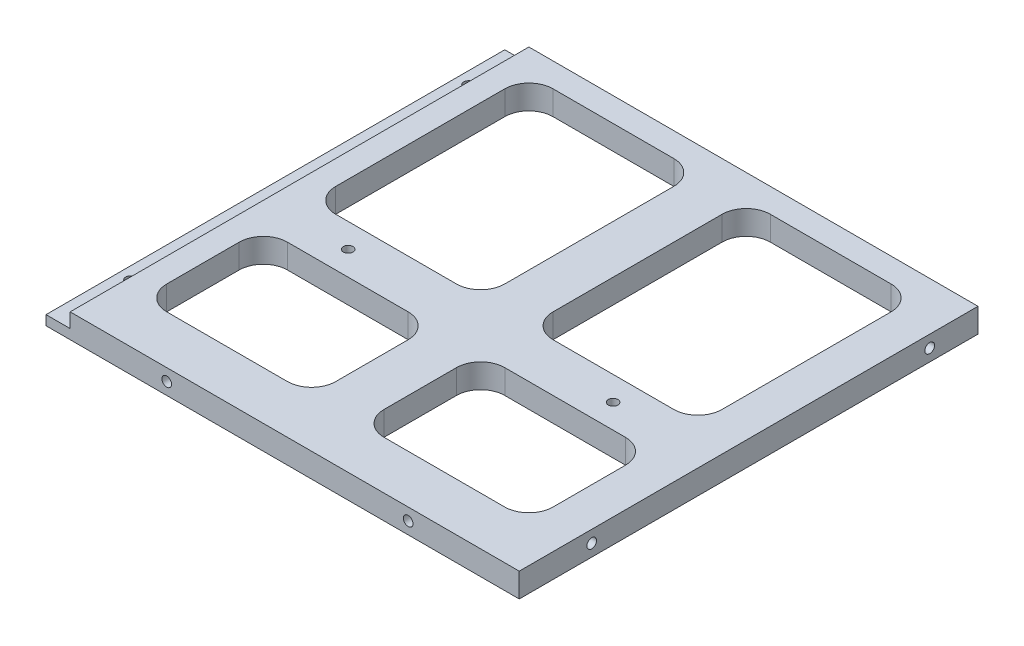
SolidWorks part; units mm, degrees
ref_plane "Front Plane" through (0, 0, 0) normal (0, 0, 1) x (1, 0, 0)
ref_plane "Top Plane" through (0, 0, 0) normal (0, 1, 0) x (1, 0, 0)
ref_plane "Right Plane" through (0, 0, 0) normal (1, 0, 0) x (0, 0, -1)
sketch "Sketch1" plane through (0, 0, 0) normal (0, 1, 0) x (1, 0, 0)
  line L1 (0, 0) -> (98, 0)
  line L2 (0, 0) -> (0, 95)
  line L3 (0, 95) -> (98, 95)
  line L4 (98, 0) -> (98, 95)
  dimension "D1" = 95
  dimension "D2" = 98
extrude "Boss-Extrude1" add sketch "Sketch1" along normal blind 5
sketch "Sketch5" plane through (0, 5, 0) normal (0, 1, 0) x (1, 0, 0)
  line L0 (98, 95) -> (0, 95) construction
  line L1 (15, 90) -> (40, 90)
  line L2 (10, 85) -> (10, 50)
  line L3 (15, 45) -> (40, 45)
  line L4 (45, 85) -> (45, 50)
  line L5 (0, 95) -> (0, 0) construction
  line L18 (60, 90) -> (85, 90)
  line L19 (0, 0) -> (98, 0) construction
  line L20 (50, 50) -> (129.5749, 50) construction
  line L21 (55, 85) -> (55, 50)
  line L22 (60, 45) -> (85, 45)
  line L23 (90, 85) -> (90, 50)
  line L24 (60, 35) -> (85, 35)
  line L25 (15, 35) -> (40, 35)
  line L26 (10, 30) -> (10, 15)
  line L27 (15, 10) -> (40, 10)
  line L28 (45, 30) -> (45, 15)
  line L29 (55, 30) -> (55, 15)
  line L30 (60, 10) -> (85, 10)
  line L31 (90, 30) -> (90, 15)
  arc A0 (15, 90) -> (10, 85) centre (15, 85) ccw
  arc A1 (10, 50) -> (15, 45) centre (15, 50) ccw
  arc A2 (40, 45) -> (45, 50) centre (40, 50) ccw
  arc A3 (40, 90) -> (45, 85) centre (40, 85) cw
  arc A4 (60, 90) -> (55, 85) centre (60, 85) ccw
  arc A5 (55, 50) -> (60, 45) centre (60, 50) ccw
  arc A6 (85, 45) -> (90, 50) centre (85, 50) ccw
  arc A7 (85, 90) -> (90, 85) centre (85, 85) cw
  arc A8 (10, 15) -> (15, 10) centre (15, 15) ccw
  arc A9 (40, 10) -> (45, 15) centre (40, 15) ccw
  arc A10 (40, 35) -> (45, 30) centre (40, 30) cw
  arc A11 (15, 35) -> (10, 30) centre (15, 30) ccw
  arc A12 (55, 15) -> (60, 10) centre (60, 15) ccw
  arc A13 (85, 10) -> (90, 15) centre (85, 15) ccw
  arc A14 (85, 35) -> (90, 30) centre (85, 30) cw
  arc A15 (60, 35) -> (55, 30) centre (60, 30) ccw
  point P55 (50, 50)
  dimension "D1" = 5
  dimension "D14" = 5
  dimension "D2" = 45
  dimension "D3" = 35
  dimension "D4" = 5
  dimension "D5" = 10
  dimension "D7" = 10
  dimension "D8" = 50
  dimension "D9" = 50
  dimension "D10" = 10
  dimension "D11" = 35
  dimension "D12" = 10
  dimension "D13" = 10
  dimension "D16" = 10
  dimension "D6" = 2
  dimension "D15" = 2
sketch "Sketch6" plane through (0, 5, 0) normal (0, 1, 0) x (1, 0, 0)
  line L0 (0, 0) -> (98, 0) construction
  line L1 (0, 95) -> (5, 95)
  line L2 (0, 95) -> (0, 0)
  line L3 (0, 0) -> (5, 0)
  line L4 (5, 95) -> (5, 0)
  dimension "D1" = 5
extrude "Cut-Extrude1" cut sketch "Sketch6" against normal blind 3
extrude "Cut-Extrude2" cut sketch "Sketch5" against normal through all
sketch "Sketch8" plane through (0, 5, 0) normal (0, 1, 0) x (1, 0, 0)
  line L2 (15, 45) -> (40, 45) construction
  line L3 (50, 50) -> (38.1732, 50) construction
  line L4 (50, 50) -> (50, 63.7417) construction
  line L5 (0, 95) -> (0, 0) construction
  line L6 (5, 0) -> (98, 0) construction
  point P2 (77.432, 40)
  point P17 (50, 50)
  point P20 (22.568, 40)
  dimension "D1" = 5
  dimension "D2" = 50
  dimension "D4" = 50
  dimension "D3" = 27.432
hole_wizard "Tap Drill for M2x0.4 Tap4" positions "3DSketch4" profile "Sketch16" hole size "M2x0.4" standard "ANSI Metric" end condition through all
sketch3d "3DSketch4"
  point P15 (22.568, 5, -40)
  point P18 (77.432, 5, -40)
sketch "Sketch16" plane through (22.568, 5, -40) normal (1, 0, 0) x (0, 0, 1)
  line L0 (0, 0) -> (0, 5)
  line L1 (0, 5) -> (1, 5)
  line L2 (1, 5) -> (1, 0)
  line L5 (1, 0) -> (0, 0)
  line L11 (0, -6.35) -> (0, 107.95) construction
  dimension "Thru Hole Dia." = 2
  dimension "Thru Hole Depth" = 5
sketch "Sketch11" plane through (0, 0, 0) normal (0, -1, 0) x (1, 0, 0)
  line L0 (0, -95) -> (0, 0) construction
  line L8 (0, 0) -> (98, 0) construction
  point P0 (2.5, -15)
  point P6 (2.5, -85)
  dimension "D1" = 2.5
  dimension "D2" = 70
  dimension "D3" = 15
  dimension "D4" = 2.5
hole_wizard "Tap Drill for M2x0.4 Tap1" positions "3DSketch2" profile "Sketch12" hole size "M2x0.4" standard "ANSI Metric" end condition through all
sketch3d "3DSketch2"
  point P0 (2.5, 0, -15)
  point P7 (2.5, 0, -85)
sketch "Sketch12" plane through (2.5, 0, -15) normal (1, 0, 0) x (0, 0, -1)
  line L0 (0, 0) -> (0, 5)
  line L1 (0, 5) -> (1, 5)
  line L2 (1, 5) -> (1, 1.1)
  line L3 (1, 1.1) -> (2.1, 0)
  line L5 (2.1, 0) -> (0, 0)
  line L6 (-1, 1.1) -> (-2.1, 0) construction
  line L11 (0, -6.35) -> (0, 107.95) construction
  dimension "Thru Hole Dia." = 2
  dimension "Thru Hole Depth" = 5
  dimension "Near C'Sink Dia." = 4.2
  dimension "Near C'Sink Angle" = 90
sketch "Sketch14" plane through (98, 0, 0) normal (1, 0, 0) x (0, 0, -1)
  line L0 (50, 5) -> (50, 0) construction
  line L1 (0, 5) -> (95, 5) construction
  line L4 (0, 5) -> (0, 0) construction
  point P6 (15, 2.5)
  point P7 (85, 2.5)
  dimension "D1" = 2.5
  dimension "D2" = 35
  dimension "D3" = 50
hole_wizard "Tap Drill for M2x0.4 Tap3" positions "3DSketch3" profile "Sketch15" hole size "M2x0.4" standard "ANSI Metric"
sketch3d "3DSketch3"
  point P0 (98, 2.5, -15)
  point P3 (98, 2.5, -85)
sketch "Sketch15" plane through (98, 2.5, -15) normal (0, 1, 0) x (0, 0, -1)
  line L0 (0, 0) -> (0, 6.6009)
  line L1 (0, 6.6009) -> (1, 6)
  line L2 (1, 6) -> (1, 0)
  line L5 (1, 0) -> (0, 0)
  line L10 (0, 6.6009) -> (-1, 6) construction
  line L11 (0, -6.35) -> (0, 107.95) construction
  dimension "Hole Dia." = 2
  dimension "Hole Depth" = 6
  dimension "Drill Angle" = 118
sketch "Sketch17" plane through (0, 0, -95) normal (0, 0, -1) x (-1, 0, 0)
  line L0 (-98, 0) -> (0, 0) construction
  line L1 (0, 2) -> (0, 0) construction
  line L2 (-50, 9.0434) -> (-50, -3.8001) construction
  point P0 (-7.25, 2.5)
  point P7 (-92.75, 2.5)
  dimension "D1" = 2.5
  dimension "D2" = 7.25
  dimension "D3" = 50
hole_wizard "Tap Drill for M2x0.4 Tap5" positions "3DSketch5" profile "Sketch18" hole size "M2x0.4" standard "ANSI Metric"
sketch3d "3DSketch5"
  point P0 (92.75, 2.5, -95)
  point P3 (7.25, 2.5, -95)
sketch "Sketch18" plane through (92.75, 2.5, -95) normal (1, 0, 0) x (0, 1, 0)
  line L0 (0, 0) -> (0, 4.6009)
  line L1 (0, 4.6009) -> (1, 4)
  line L2 (1, 4) -> (1, 0)
  line L5 (1, 0) -> (0, 0)
  line L10 (0, 4.6009) -> (-1, 4) construction
  line L11 (0, -6.35) -> (0, 107.95) construction
  dimension "Hole Dia." = 2
  dimension "Hole Depth" = 4
  dimension "Drill Angle" = 118
sketch "Sketch19" plane through (0, 0, 0) normal (0, 0, 1) x (1, 0, 0)
  line L0 (0, 0) -> (98, 0) construction
  line L1 (0, 2) -> (0, 0) construction
  line L2 (50, -5.0975) -> (50, 9.6857) construction
  point P0 (25, 2.5)
  point P7 (75, 2.5)
  dimension "D1" = 2.5
  dimension "D2" = 25
  dimension "D3" = 50
hole_wizard "Tap Drill for M2x0.4 Tap6" positions "3DSketch6" profile "Sketch20" hole size "M2x0.4" standard "ANSI Metric"
sketch3d "3DSketch6"
  point P0 (25, 2.5, 0)
  point P3 (75, 2.5, 0)
sketch "Sketch20" plane through (25, 2.5, 0) normal (1, 0, 0) x (0, -1, 0)
  line L0 (0, 0) -> (0, 7.6009)
  line L1 (0, 7.6009) -> (1, 7)
  line L2 (1, 7) -> (1, 0)
  line L5 (1, 0) -> (0, 0)
  line L10 (0, 7.6009) -> (-1, 7) construction
  line L11 (0, -6.35) -> (0, 107.95) construction
  dimension "Hole Dia." = 2
  dimension "Hole Depth" = 7
  dimension "Drill Angle" = 118
